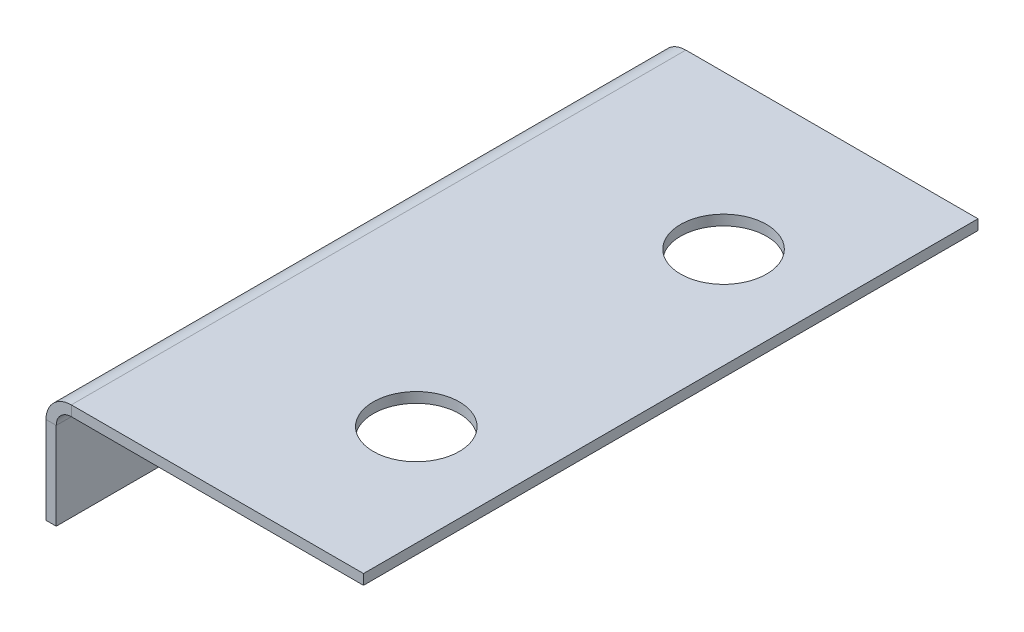
SolidWorks part; units mm, degrees
note: The reader was unsure of these and kept them because the rebuilt part matched: flange length of "Edge-Flange1".
ref_plane "Front Plane" through (0, 0, 0) normal (0, 0, 1) x (1, 0, 0)
ref_plane "Top Plane" through (0, 0, 0) normal (0, 1, 0) x (1, 0, 0)
ref_plane "Right Plane" through (0, 0, 0) normal (1, 0, 0) x (0, 0, -1)
sketch "Sketch1" plane through (0, 0, 0) normal (0, 1, 0) x (1, 0, 0)
  line L1 (2.981, 16.8144) -> (17.981, 16.8144)
  line L2 (2.981, 16.8144) -> (2.981, -13.1856)
  line L3 (2.981, -13.1856) -> (17.981, -13.1856)
  line L4 (17.981, 16.8144) -> (17.981, -13.1856)
  circle A0 centre (13.0588, -5.6856) radius 2.1
  circle A1 centre (13.0588, 9.3144) radius 2.1
  dimension "D3" = 15
  dimension "D4" = 4.2
  dimension "D5" = 4.2
  dimension "D1" = 30
  dimension "D2" = 15
  dimension "D6" = 7.5
  dimension "D7" = 7.5
sheet metal parameters "Sheet-Metal1" thickness 0.5 parameters "D1"=0.7366
base flange "Base-Flange1" sketch "Sketch1" thickness 0.5 reverse thickness direction no parameters "D1"=0.7366
edge flange "Edge-Flange1" sketch "Sketch7" flange angle 90 flange length 5 flange position material outside bend radius 0.7366 thickness 0.5 relief rectangular parameters "D6"=10
sketch "Sketch7" plane through (2.981, -0.5, 0) normal (-1, 0, 0) x (0, 0, -1)
  line L0 (16.8144, 0) -> (-13.1856, 0) construction
  line L1 (16.8144, 0) -> (-13.1856, 0)
  line L2 (-13.1856, 0) -> (-13.1856, 5)
  line L3 (-13.1856, 5) -> (16.8144, 5)
  line L4 (16.8144, 5) -> (16.8144, 0)
bend "EdgeBend1" bend radius 0.7366 bend angle 90 parameters "D5"=1
sketch "Sketch8" plane through (2.981, 0, 0) normal (1, 0, 0) x (0, 0, -1)
  line L1 (16.8144, -5.5) -> (-13.1856, -5.5) construction
  circle A0 centre (5.1144, -3.5) radius 1.1
  circle A1 centre (-1.4856, -3.5) radius 1.1
  dimension "D3" = 2.2
  dimension "D4" = 2.2
  dimension "D5" = 2
  dimension "D6" = 2
extrude "Cut-Extrude1" cut sketch "Sketch8" against normal blind 10 normal cut yes
flat pattern "Flat-Pattern1" [suppressed]
sketch "Bend-Lines1" plane through (0, 0, 0) normal (0, 1, 0) x (1, 0, 0)
sketch3d "Bounding-Box1" [suppressed]
  line L0 (-7.9758, 17.0407, 0) -> (-7.9758, -12.9593, 0) construction
  line L1 (-17.9758, 17.0407, 0) -> (-17.9758, -12.9593, 0) construction
  line L2 (-7.9758, 17.0407, 0) -> (-17.9758, 17.0407, 0) construction
  line L3 (-7.9758, -12.9593, 0) -> (-17.9758, -12.9593, 0) construction
bend of the flat pattern "Flatten-<EdgeBend1>1"
